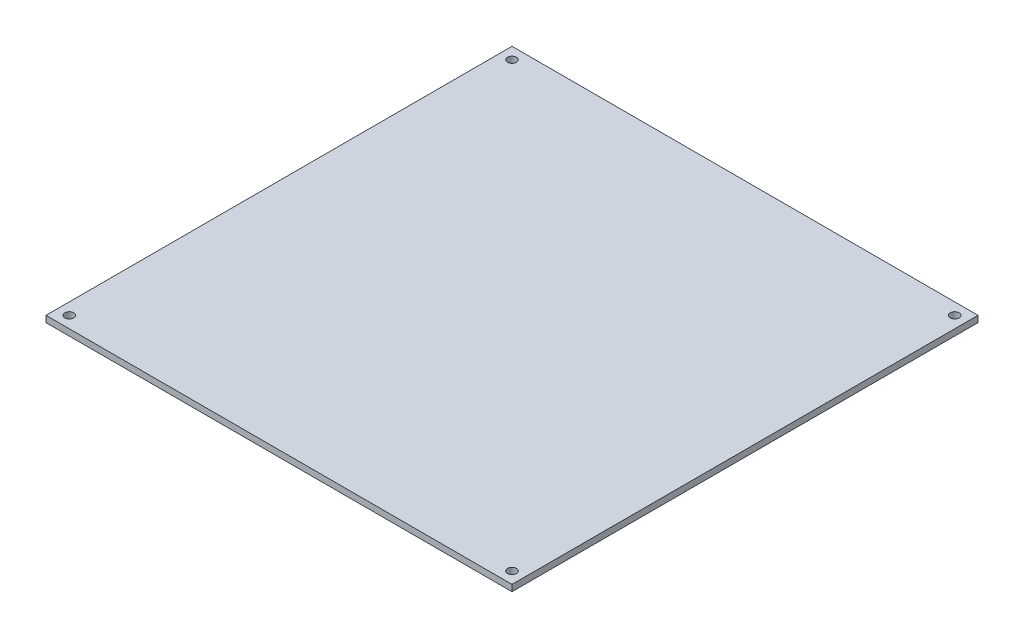
SolidWorks part; units mm, degrees
ref_plane "Front Plane" through (0, 0, 0) normal (0, 0, 1) x (1, 0, 0)
ref_plane "Top Plane" through (0, 0, 0) normal (0, 1, 0) x (1, 0, 0)
ref_plane "Right Plane" through (0, 0, 0) normal (1, 0, 0) x (0, 0, -1)
sketch "Sketch1" plane through (0, 0, 0) normal (0, 1, 0) x (1, 0, 0)
  line L1 (-110, -110) -> (110, -110)
  line L2 (-110, -110) -> (-110, 110)
  line L3 (-110, 110) -> (110, 110)
  line L4 (110, -110) -> (110, 110)
  line L5 (-110, -110) -> (110, 110) construction
  line L6 (-110, 110) -> (110, -110) construction
  circle A0 centre (-104.5, 104.5) radius 2.1
  circle A1 centre (104.5, 104.5) radius 2.1
  circle A2 centre (104.5, -104.5) radius 2.1
  circle A3 centre (-104.5, -104.5) radius 2.1
  point P0 (0, 0)
  dimension "D2" = 5.5
  dimension "D1" = 220
  dimension "D3" = 2
extrude "Boss-Extrude1" add sketch "Sketch1" along normal blind 3
